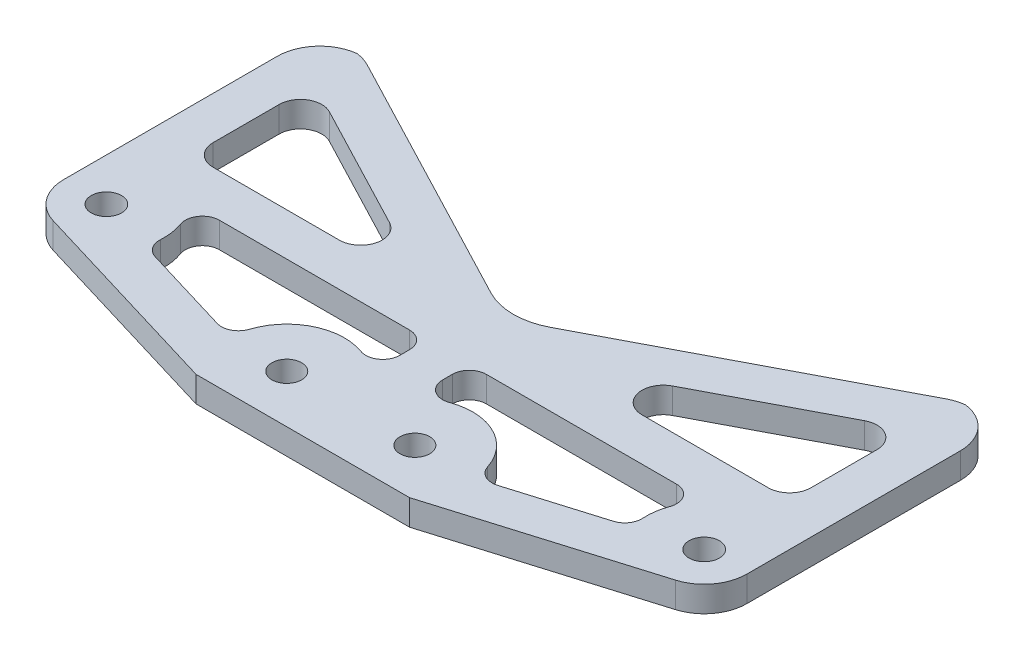
SolidWorks part; units mm, degrees
material "Custom Plastic"
ref_plane "Front Plane" through (0, 0, 0) normal (0, 0, 1) x (1, 0, 0)
ref_plane "Top Plane" through (0, 0, 0) normal (0, 1, 0) x (1, 0, 0)
ref_plane "Right Plane" through (0, 0, 0) normal (1, 0, 0) x (0, 0, -1)
sketch "Sketch1" plane through (0, 0, 0) normal (0, 1, 0) x (1, 0, 0)
  line L1 (-50.8, -34.925) -> (50.8, -34.925)
  line L2 (-50.8, -34.925) -> (-50.8, 34.925)
  line L3 (-50.8, 34.925) -> (50.8, 34.925)
  line L4 (50.8, -34.925) -> (50.8, 34.925)
  line L5 (-50.8, -34.925) -> (50.8, 34.925) construction
  line L6 (-50.8, 34.925) -> (50.8, -34.925) construction
  point P0 (0, 0)
  dimension "D1" = 101.6
  dimension "D2" = 69.85
extrude "Base" add sketch "Sketch1" along normal blind 3.81
sketch "Sketch2" plane through (0, 3.81, 0) normal (0, 1, 0) x (1, 0, 0)
  line L0 (-44.45, 34.925) -> (0, 11.6802)
  line L1 (50.8, 34.925) -> (-50.8, 34.925) construction
  line L2 (0, 11.6802) -> (44.45, 34.925)
  line L3 (-44.45, 34.925) -> (44.45, 34.925)
  line L4 (0, 0) -> (0, 34.925) construction
  circle A0 centre (0, 20.6375) radius 7.9375 construction
  dimension "D1" = 15.875
  dimension "D2" = 88.9
  dimension "D3" = 14.2875
extrude "Tube notch" cut sketch "Sketch2" against normal through all
sketch "Sketch3" plane through (0, 3.81, 0) normal (0, 1, 0) x (1, 0, 0)
  line L1 (0, 0) -> (0, -34.925) construction
  line L2 (-44.45, -3.175) -> (44.45, -3.175) construction
  line L3 (-44.45, -3.175) -> (-44.45, -28.575) construction
  line L4 (-44.45, -28.575) -> (44.45, -28.575) construction
  line L5 (44.45, -3.175) -> (44.45, -28.575) construction
  line L6 (-50.8, -34.925) -> (50.8, -34.925) construction
  line L7 (-50.8, 3.175) -> (50.8, 3.175) construction
  line L8 (-50.8, 34.925) -> (-50.8, -34.925) construction
  line L9 (50.8, -34.925) -> (50.8, 34.925) construction
  point P9 (0, -3.175)
  dimension "D1" = 88.9
  dimension "D2" = 6.35
  dimension "D3" = 25.4
  dimension "D4" = 6.35
hole_wizard "Mounting holes" positions "Sketch5" profile "Sketch4" hole size "#8" standard "ANSI Inch" end condition through all
sketch "Sketch5" plane through (0, 3.81, 0) normal (0, 1, 0) x (1, 0, 0)
  point P0 (-44.45, -3.175)
  point P9 (44.45, -3.175)
sketch "Sketch4" plane through (-44.45, 3.81, 3.175) normal (1, 0, 0) x (0, 0, 1)
  line L0 (0, 0) -> (0, 3.81)
  line L1 (0, 3.81) -> (2.2479, 3.81)
  line L2 (2.2479, 3.81) -> (2.2479, 0)
  line L5 (2.2479, 0) -> (0, 0)
  line L11 (0, -6.35) -> (0, 107.95) construction
  dimension "Thru Hole Dia." = 4.4958
  dimension "Thru Hole Depth" = 3.81
sketch "Sketch8" plane through (0, 3.81, 0) normal (0, 1, 0) x (1, 0, 0)
  line L0 (-50.8, -34.925) -> (50.8, -34.925) construction
  line L1 (-38.1, -34.925) -> (38.1, -34.925)
  line L2 (-38.1, -34.925) -> (-38.1, 3.175)
  line L3 (-38.1, 3.175) -> (38.1, 3.175)
  line L4 (38.1, -34.925) -> (38.1, 3.175)
  line L5 (-50.8, -9.525) -> (-38.1, -9.525)
  line L6 (-50.8, 34.925) -> (-50.8, -34.925) construction
  line L8 (38.1, -9.525) -> (50.8, -9.525)
  line L9 (50.8, -34.925) -> (50.8, 34.925) construction
  line L10 (50.8, -9.525) -> (50.8, -34.925)
  line L11 (50.8, -34.925) -> (38.1, -34.925)
  line L12 (-38.1, -34.925) -> (-50.8, -34.925)
  line L13 (-50.8, -34.925) -> (-50.8, -9.525)
  circle A0 centre (-44.45, -3.175) radius 2.2479 construction
  point P6 (0, 3.175)
  line M5 (50.8, -34.925) -> (50.8, 34.925)
  line M10 (-50.8, 34.925) -> (-50.8, -34.925)
  line M11 (-50.8, -34.925) -> (50.8, -34.925)
  dimension "D3" = 6.35
  dimension "D1" = 38.1
  dimension "D2" = 76.2
extrude "Wheel cutout" cut sketch "Sketch8" against normal through all contours L5 L2 M10 M11 | L4 L3 L2 M11 | L8 L4 M11 M5 region at (0, 3.81, 15.875) region at (-44.45, 3.81, 22.225) region at (44.45, 3.81, 22.225)
fillet "Fillet1" radius 6.35 10 edges at (-44.45, 1.905, -34.925) (44.45, 1.905, -34.925) (50.8, 1.905, -34.925) (38.1, 1.905, -3.175) (-38.1, 1.905, -3.175) (-50.8, 1.905, -34.925) (50.8, 1.905, 9.525) (38.1, 1.905, 9.525) (-50.8, 1.905, 9.525) (-38.1, 1.905, 9.525)
fillet "Fillet2" radius 9.525 1 edges at (0, 1.905, -11.6802)
sketch "Sketch9" plane through (0, 3.81, 0) normal (0, 1, 0) x (1, 0, 0)
  line L0 (-44.45, 9.525) -> (-44.45, 27.7591)
  line L1 (-44.45, 27.7591) -> (-9.5817, 9.525)
  line L2 (9.5817, 9.525) -> (44.45, 27.7591)
  line L3 (44.45, 27.7591) -> (44.45, 9.525)
  line L4 (44.45, 9.525) -> (9.5817, 9.525)
  line L5 (-43.0675, 34.202) -> (-4.4139, 13.9884) construction
  line L6 (-50.8, 28.575) -> (-50.8, -3.175) construction
  line L7 (31.75, 3.175) -> (-31.75, 3.175) construction
  line L10 (-9.5817, 9.525) -> (-44.45, 9.525)
  line L11 (4.4139, 13.9884) -> (43.0675, 34.202) construction
  line L12 (50.8, -3.175) -> (50.8, 28.575) construction
  dimension "D1" = 6.35
  dimension "D2" = 6.35
  dimension "D3" = 6.35
  dimension "D5" = 6.35
extrude "Cut-Extrude1" cut sketch "Sketch9" against normal through all
fillet "Fillet3" radius 3.175 6 edges at (-44.45, 1.905, -9.525) (44.45, 1.905, -9.525) (44.45, 1.905, -27.7591) (-44.45, 1.905, -27.7591) (9.5817, 1.905, -9.525) (-9.5817, 1.905, -9.525)
sketch "Sketch10" plane through (0, 3.81, 0) normal (0, 1, 0) x (1, 0, 0)
  line L0 (-46.2816, -9.2551) -> (-15.875, -18.415)
  line L1 (-15.875, -18.415) -> (15.875, -18.415)
  line L2 (15.875, -18.415) -> (46.2816, -9.2551)
  line L3 (0, 3.175) -> (0, -18.415) construction
  line L4 (-31.75, 3.175) -> (31.75, 3.175) construction
  line L5 (-46.2816, -9.2551) -> (-38.1, -3.175)
  line L6 (46.2816, -9.2551) -> (38.1, -3.175)
  line L7 (-31.75, 3.175) -> (31.75, 3.175)
  arc A0 (-50.8, -3.175) -> (-44.45, -9.525) centre (-44.45, -3.175) ccw construction
  arc A1 (44.45, -9.525) -> (50.8, -3.175) centre (44.45, -3.175) ccw construction
  arc A2 (-31.75, 3.175) -> (-38.1, -3.175) centre (-31.75, -3.175) ccw construction
  arc A3 (38.1, -3.175) -> (31.75, 3.175) centre (31.75, -3.175) ccw construction
  arc A4 (-31.75, 3.175) -> (-38.1, -3.175) centre (-31.75, -3.175) ccw
  arc A5 (38.1, -3.175) -> (31.75, 3.175) centre (31.75, -3.175) ccw
  dimension "D1" = 31.75
  dimension "D2" = 21.59
extrude "Boss-Extrude2" add sketch "Sketch10" against normal through all
sketch "Sketch11" plane through (0, 3.81, 0) normal (0, 1, 0) x (1, 0, 0)
  circle A0 centre (-9.525, -11.2753) radius 2.2099
  circle A1 centre (9.525, -11.2753) radius 2.2099
  arc A2 (-9.525, -9.0654) -> (-9.525, -13.4852) centre (-9.525, -11.2753) ccw construction
  point P0 (-9.525, -11.2753)
  point P1 (9.525, -11.2753)
extrude "Cut-Extrude3" cut sketch "Sketch11" against normal through all
sketch "Sketch12" plane through (0, 3.81, 0) normal (0, 1, 0) x (1, 0, 0)
  line L0 (-44.45, -3.175) -> (-14.9393, -12.065) construction
  line L1 (-14.9393, -12.065) -> (14.9393, -12.065) construction
  line L2 (0, -12.065) -> (0, 3.175) construction
  line L3 (44.45, 3.175) -> (-44.45, 3.175) construction
  line L4 (-44.45, 3.175) -> (-44.45, -3.175) construction
  line L5 (-50.8, 28.575) -> (-50.8, -3.175) construction
  line L6 (-46.2816, -9.2551) -> (-15.875, -18.415) construction
  line L7 (-15.875, -18.415) -> (15.875, -18.415) construction
  line L8 (-34.0665, -6.303) -> (-20.8559, -10.2826)
  line L9 (-41.275, 9.525) -> (-22.5046, 9.525) construction
  line L10 (-44.45, 22.5159) -> (-44.45, 12.7) construction
  line L11 (-3.175, 3.175) -> (-3.175, -12.065) construction
  line L12 (-33.984, 3.175) -> (-5.715, 3.175)
  line L13 (-3.175, 0.635) -> (-3.175, -0.8093)
  line L14 (3.175, 3.175) -> (3.175, -12.065) construction
  line L15 (44.45, 3.175) -> (44.45, -3.175) construction
  line L16 (44.45, -3.175) -> (14.9393, -12.065) construction
  line L17 (3.175, 0.635) -> (3.175, -0.8093)
  line L18 (33.984, 3.175) -> (5.715, 3.175)
  line L19 (34.0665, -6.303) -> (20.8559, -10.2826)
  arc A0 (-35.8689, -3.7122) -> (-36.3708, -0.2339) centre (-44.45, -3.175) ccw
  circle A1 centre (-44.45, -3.175) radius 2.2479 construction
  arc A2 (-17.7064, -8.6316) -> (-6.5839, -3.1961) centre (-9.525, -11.2753) cw
  arc A3 (-5.715, 3.175) -> (-3.175, 0.635) centre (-5.715, 0.635) cw
  arc A4 (-6.5839, -3.1961) -> (-3.175, -0.8093) centre (-5.715, -0.8093) ccw
  arc A5 (-17.7064, -8.6316) -> (-20.8559, -10.2826) centre (-20.1233, -7.8506) cw
  arc A6 (-35.8689, -3.7122) -> (-34.0665, -6.303) centre (-33.3339, -3.871) ccw
  arc A7 (-36.3708, -0.2339) -> (-33.984, 3.175) centre (-33.984, 0.635) cw
  arc A8 (36.3708, -0.2339) -> (33.984, 3.175) centre (33.984, 0.635) ccw
  arc A9 (35.8689, -3.7122) -> (34.0665, -6.303) centre (33.3339, -3.871) cw
  arc A10 (17.7064, -8.6316) -> (20.8559, -10.2826) centre (20.1233, -7.8506) ccw
  arc A11 (6.5839, -3.1961) -> (3.175, -0.8093) centre (5.715, -0.8093) cw
  arc A12 (5.715, 3.175) -> (3.175, 0.635) centre (5.715, 0.635) ccw
  arc A13 (17.7064, -8.6316) -> (6.5839, -3.1961) centre (9.525, -11.2753) ccw
  arc A14 (35.8689, -3.7122) -> (36.3708, -0.2339) centre (44.45, -3.175) cw
  point P31 (-3.175, -5.4786)
  point P34 (-18.1212, -11.1065)
  point P37 (-36.2175, -5.655)
  point P40 (-38.6533, 3.175)
  point P62 (38.6533, 3.175)
  point P63 (36.2175, -5.655)
  point P64 (18.1212, -11.1065)
  point P65 (3.175, -5.4786)
  dimension "D4" = 6.35
  dimension "D6" = 2.54
  dimension "D1" = 6.35
  dimension "D2" = 6.35
  dimension "D3" = 6.35
  dimension "D5" = 3.175
extrude "Cut-Extrude4" cut sketch "Sketch12" against normal through all
equation "\"MAT_THICKNESS\"=0.1"
